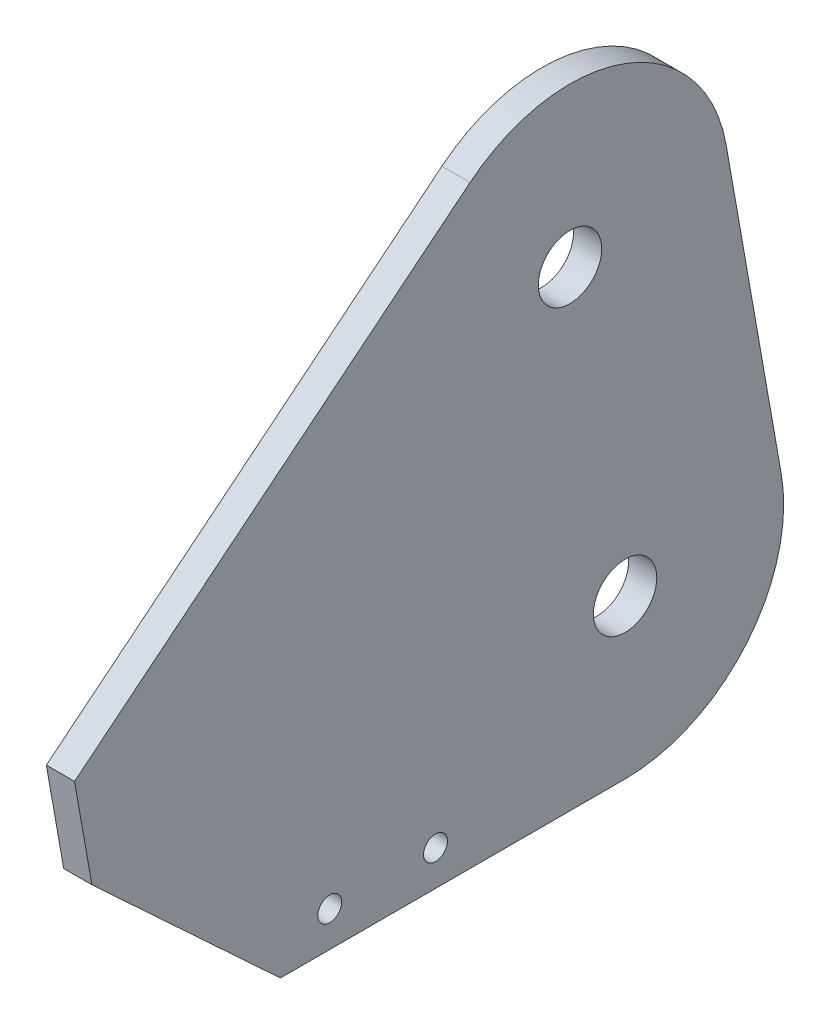
SolidWorks part; units mm, degrees
ref_plane "Front Plane" through (0, 0, 0) normal (0, 0, 1) x (1, 0, 0)
ref_plane "Top Plane" through (0, 0, 0) normal (0, 1, 0) x (1, 0, 0)
ref_plane "Right Plane" through (0, 0, 0) normal (1, 0, 0) x (0, 0, -1)
ref_plane "Plane1" through (-18, 0, 0) normal (-1, 0, 0) x (0, 0, 1)
sketch "Sketch2" plane through (-18, 0, 0) normal (-1, 0, 0) x (0, 0, 1)
  line L0 (48.7484, 82.0825) -> (51.2055, 96.0176) construction
  line L1 (22, 57.2579) -> (48.7484, 82.0825) construction
  line L2 (-26.8968, 57.2579) -> (22, 57.2579) construction
  line L3 (-41.2408, 127.9813) -> (-49.0549, 83.6649) construction
  line L4 (48.7484, 82.0825) -> (51.2055, 96.0176)
  line L5 (-41.2408, 127.9813) -> (-49.0549, 83.6649)
  line L6 (-26.8968, 57.2579) -> (22, 57.2579)
  line L7 (22, 57.2579) -> (48.7484, 82.0825)
  line L8 (48.7484, 82.0825) -> (51.2055, 96.0176)
  line L9 (51.2055, 96.0176) -> (-4.9059, 141.5462)
  line L10 (-41.2408, 127.9813) -> (-49.0549, 83.6649)
  line L11 (-26.8968, 57.2579) -> (22, 57.2579)
  line L12 (22, 57.2579) -> (48.7484, 82.0825)
  line L13 (48.7484, 82.0825) -> (51.2055, 96.0176)
  line L14 (51.2055, 96.0176) -> (-4.9059, 141.5462)
  line L15 (22, 57.2579) -> (48.7484, 82.0825)
  line L16 (-26.8968, 57.2579) -> (22, 57.2579)
  line L17 (-41.2408, 127.9813) -> (-49.0549, 83.6649)
  circle A0 centre (-26.8968, 79.7579) radius 22.5 construction
  circle A1 centre (-19.0826, 124.0742) radius 22.5 construction
  arc A2 (-4.9059, 141.5462) -> (-41.2408, 127.9813) centre (-19.0826, 124.0742) ccw
  arc A3 (-49.0549, 83.6649) -> (-26.8968, 57.2579) centre (-26.8968, 79.7579) ccw
  arc A4 (-4.9059, 141.5462) -> (-41.2408, 127.9813) centre (-19.0826, 124.0742) ccw
  arc A5 (-49.0549, 83.6649) -> (-26.8968, 57.2579) centre (-26.8968, 79.7579) ccw
  arc A6 (-49.0549, 83.6649) -> (-26.8968, 57.2579) centre (-26.8968, 79.7579) ccw
  arc A7 (-4.9059, 141.5462) -> (-41.2408, 127.9813) centre (-19.0826, 124.0742) ccw
  dimension "D1" = 0
extrude "Boss-Extrude1" add sketch "Sketch2" along normal blind 4 contours L10 A5 L11 L12 L4 L14 A4 region at (-18, 96.1841, -5.0718)
hole_wizard "Hole1" positions "Sketch3" profile "Sketch4" legacy end condition through all
sketch "Sketch3" plane through (-18, 0, 0) normal (1, 0, 0) x (0, 0, -1)
  point P0 (19.0826, 124.0742)
  point P3 (26.8968, 79.7579)
sketch "Sketch4" plane through (-18, 124.0742, -19.0826) normal (0, 1, 0) x (0, 0, -1)
  line L0 (0, 0) -> (0, 4)
  line L1 (0, 4) -> (4.5, 4)
  line L2 (4.5, 4) -> (4.5, 0)
  line L3 (4.5, 0) -> (0, 0)
  line L4 (0, 110) -> (0, -10) construction
  dimension "Diameter" = 9
  dimension "Depth" = 4
hole_wizard "M3 Clearance Hole1" positions "Sketch5" profile "Sketch6" hole size "M3" standard "ANSI Metric" end condition through all
sketch "Sketch5" plane through (-22, 0, 0) normal (-1, 0, 0) x (0, 0, 1)
  point P0 (15, 62.2579)
  point P3 (0, 62.2579)
sketch "Sketch6" plane through (-22, 62.2579, 15) normal (0, 1, 0) x (0, 0, 1)
  line L0 (0, 0) -> (0, 4)
  line L1 (0, 4) -> (1.7, 4)
  line L2 (1.7, 4) -> (1.7, 0.025)
  line L3 (1.7, 0.025) -> (1.725, 0)
  line L5 (1.725, 0) -> (0, 0)
  line L6 (-1.7, 0.025) -> (-1.725, 0) construction
  line L11 (0, -6.35) -> (0, 107.95) construction
  dimension "Thru Hole Dia." = 3.4
  dimension "Thru Hole Depth" = 4
  dimension "Near C'Sink Dia." = 3.45
  dimension "Near C'Sink Angle" = 90
